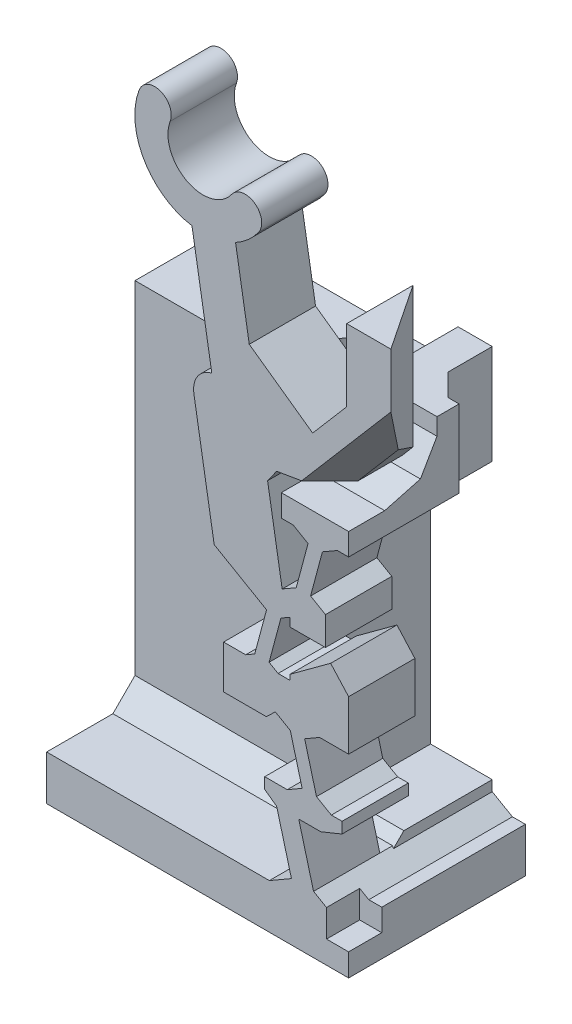
SolidWorks part; units mm, degrees
material "Nylon 6/12"
ref_plane "Front Plane" through (0, 0, 0) normal (0, 0, 1) x (1, 0, 0)
ref_plane "Top Plane" through (0, 0, 0) normal (0, 1, 0) x (1, 0, 0)
ref_plane "Right Plane" through (0, 0, 0) normal (1, 0, 0) x (0, 0, -1)
sketch "Sketch-SkeletonConfigUp" plane through (0, 0, 0) normal (0, 0, 1) x (1, 0, 0)
  line L0 (0, 0) -> (0, -50000) construction
  line L1 (0, 0) -> (4.5811, 6.2164) construction
  line L2 (9.8143, 13.3177) -> (4.5811, 13.945) construction
  line L3 (4.5811, 13.945) -> (2.9713, 10.4094) construction
  line L4 (2.9713, 10.4094) -> (4.5811, 6.2164) construction
  line L5 (4.5811, 13.945) -> (6.2429, 19.1409) construction
  line L6 (2.9713, 10.4094) -> (0.0405, 27.8193) construction
  line L7 (4.5811, 6.2164) -> (9.8143, 13.3177) construction
  line L8 (-587.3593, -797.0242) -> (9.8143, 13.3177) construction
  dimension "D2" = 7.7221
  dimension "D3" = 8.8212
  dimension "D4" = 5.2707
  dimension "D5" = 119.553
  dimension "D6" = 3.8848
  dimension "D7" = 5.4552
  dimension "D8" = 17.6549
  dimension "D9" = 4.4914
  dimension "D10" = 6.745
  dimension "D11" = 145.964
  dimension "D12" = 143.612
sketch "Sketch-SkeletonConfigDown" plane through (0, 0, 0) normal (0, 0, 1) x (1, 0, 0)
  line L0 (0, 0) -> (0, -50000) construction
  line L1 (0, 0) -> (4.5811, 6.2164) construction
  line L2 (9.8143, 13.3177) -> (4.5811, 13.945) construction
  line L3 (4.5811, 13.945) -> (6.1909, 10.4094) construction
  line L4 (6.1909, 10.4094) -> (4.5811, 6.2164) construction
  line L5 (4.5811, 13.945) -> (1.753, 18.6098) construction
  line L6 (6.1909, 10.4094) -> (-8.8652, 19.6294) construction
  line L7 (4.5811, 6.2164) -> (9.8143, 13.3177) construction
  line L8 (-589.9357, -800.5203) -> (9.8143, 13.3177) construction
  dimension "D2" = 7.7221
  dimension "D3" = 8.8212
  dimension "D4" = 5.2707
  dimension "D5" = 119.553
  dimension "D6" = 3.8848
  dimension "D7" = 5.4552
  dimension "D8" = 17.6549
  dimension "D9" = 4.4914
  dimension "D10" = 6.745
  dimension "D11" = 145.964
  dimension "D1" = 143.612
ref_plane "Plane-Cam Base" through (9.128, 0, 0) normal (1, 0, 0) x (0, 0, -1)
ref_plane "Plane-Down-to-Up Derailleur Clearance" through (6.628, 0, 0) normal (1, 0, 0) x (0, 0, -1)
ref_plane "Plane-Cam Cavity Roof" through (5.128, 0, 0) normal (1, 0, 0) x (0, 0, -1)
sketch "Sketch-SwitchBossUp" plane through (0, 0, 0) normal (0, 0, 1) x (1, 0, 0)
  line L0 (3.5811, 11.4759) -> (3.5811, 12.945) construction
  line L2 (6.5405, 21.1774) -> (6.5405, 24.4384)
  line L3 (6.5405, 24.4384) -> (8.5405, 24.4384)
  line L4 (8.5405, 24.4384) -> (8.5405, 20.4384)
  line L5 (5.5811, 12.5552) -> (5.5811, 11.263)
  line L7 (1.5115, 25.1048) -> (2.5464, 18.9575)
  line L8 (-0.4607, 24.7728) -> (0.4359, 19.4465)
  line L9 (2.9713, 10.4094) -> (0.0405, 27.8193) construction
  line L11 (-0.0396, 22.2712) -> (1.9326, 22.6032) construction
  line L15 (6.628, -55) -> (6.628, 55) construction
  line L16 (2.9713, 10.4094) -> (4.5811, 6.2164) construction
  line L17 (3.5811, 12.945) -> (3.5811, 14.945) construction
  line L18 (5.5811, 12.945) -> (5.5811, 14.945) construction
  line L19 (4.2561, 13.945) -> (4.9061, 13.945) construction
  line L20 (3.5811, 14.945) -> (5.5811, 14.945) construction
  line L21 (3.5811, 12.945) -> (5.5811, 12.945) construction
  line L22 (4.5811, 12.945) -> (4.5811, 14.945) construction
  line L23 (4.5811, 6.2164) -> (8.5405, 7.1023) construction
  line L24 (1.9713, 9.4094) -> (1.9713, 11.4094) construction
  line L25 (3.9713, 9.4094) -> (3.9713, 11.4094) construction
  line L26 (3.9713, 9.4094) -> (1.9713, 9.4094) construction
  line L27 (1.9713, 11.4094) -> (3.9713, 11.4094) construction
  line L28 (3.5811, 7.2164) -> (5.5811, 7.2164) construction
  line L29 (3.5811, 7.2164) -> (3.5811, 5.2164) construction
  line L30 (5.5811, 7.2164) -> (5.5811, 5.2164) construction
  line L31 (3.5811, 5.2164) -> (5.5811, 5.2164) construction
  line L32 (4.9061, 6.2164) -> (4.2561, 6.2164) construction
  line L40 (3.2963, 10.4094) -> (2.6463, 10.4094) construction
  line L43 (2.874, 4.5093) -> (0.7934, 4.5093) construction
  line L51 (4.9929, 19.3693) -> (2.5464, 18.9575)
  line L66 (0.0405, 27.8193) -> (0.0405, 50027.8193) construction
  line L74 (0.5445, 12.7775) -> (-0.3728, 18.2264)
  line L75 (0.3841, 13.7302) -> (2.3564, 14.0622) construction
  line L76 (5.5811, 11.263) -> (5.5811, 12.5552) construction
  line L80 (5.8152, 10.763) -> (6.628, 9.8603)
  line L81 (8.5405, 1033.6218) -> (8.5405, 20.4384) construction
  line L82 (2.5464, 18.9575) -> (3.5585, 12.945) construction
  line L83 (3.6203, 12.5779) -> (2.8784, 16.9852)
  line L84 (2.8784, 16.9852) -> (6.0405, 17.5175)
  line L85 (6.9307, 9.5241) -> (8.5405, 7.7363) construction
  line L88 (3.5811, 16.3347) -> (6.8573, 16.3347)
  line L92 (3.7762, 8.3129) -> (6.9307, 9.5241) construction
  line L93 (6.3311, 4.3289) -> (5.3706, 3.937)
  line L95 (2.5464, 18.9575) -> (2.8784, 16.9852) construction
  line L96 (2.7124, 17.9713) -> (8.5405, 18.9524) construction
  line L97 (2.7124, 17.9713) -> (1.7262, 17.8053) construction
  line L98 (1.9713, 9.1744) -> (0.9713, 9.1744)
  line L99 (0.9713, 9.1744) -> (0.9713, 7.2164)
  line L100 (0.9713, 7.2164) -> (2.9061, 7.2164)
  line L101 (4.5811, 6.2164) -> (6.9307, 9.5241) construction
  line L103 (0.0405, 27.8193) -> (1.9448, 26.4638) construction
  line L104 (6.9307, 9.5241) -> (8.5405, 7.7363) construction
  line L106 (13.4416, 14.945) -> (5.5811, 14.945) construction
  line L107 (1.9713, 9.4094) -> (1.9713, 9.1744) construction
  line L109 (0.0405, 27.8193) -> (-2.1498, 28.6358) construction
  line L110 (8.5405, 20.4384) -> (6.0405, 17.5175)
  line L111 (6.628, 9.8603) -> (6.628, 8.3653)
  line L112 (6.628, 9.8603) -> (6.9307, 9.5241) construction
  line L113 (2.8311, 4.8267) -> (2.8311, 4.3267)
  line L114 (7.3693, 7.7363) -> (7.3563, 7.7363) construction
  line L115 (6.8573, 16.3347) -> (13.4416, 16.3347)
  line L116 (13.4416, 16.3347) -> (13.4416, -1.1653)
  line L117 (13.4416, -1.1653) -> (5.0405, -1.1653)
  line L119 (10.4375, 14.0252) -> (10.4375, 2.1692)
  line L121 (5.0405, -1.1653) -> (5.0405, 1.437) construction
  line L122 (8.237, 12.8031) -> (10.8393, 12.8031) construction
  line L123 (10.8393, 12.8031) -> (13.4416, 12.8031) construction
  line L124 (10.4375, 2.1692) -> (9.128, 0.8597)
  line L125 (8.5405, 7.5847) -> (13.4416, 7.5847) construction
  line L127 (5.5811, 15.3347) -> (5.5811, 14.945) construction
  line L130 (6.0405, 0.8597) -> (9.128, 0.8597)
  line L132 (2.8311, 4.3267) -> (3.3706, 3.937)
  line L133 (2.9713, 10.4094) -> (6.1909, 10.4094) construction
  line L134 (4.5811, 10.4094) -> (4.5811, 13.945) construction
  line L135 (4.5811, 10.4094) -> (4.5811, 6.2164) construction
  line L137 (3.9713, 9.4094) -> (5.5811, 7.2164) construction
  line L139 (5.8152, 10.763) -> (3.9713, 9.4094)
  line L141 (4.0405, 1.437) -> (3.0405, 0.8597)
  line L142 (3.0405, 0.8597) -> (3.0405, -1.1653)
  line L143 (8.5405, 20.4384) -> (8.5405, 18.9524) construction
  line L145 (8.5405, 17.9384) -> (8.5405, -49992.0368) construction
  line L147 (5.5811, 11.263) -> (5.5811, 12.5552) construction
  line L149 (6.3311, 4.8289) -> (6.3311, 4.3289)
  line L150 (3.0405, -1.1653) -> (5.0405, -1.1653)
  line L151 (3.3706, 3.937) -> (5.3706, 3.937) construction
  line L152 (4.792, 14.945) -> (4.2561, 12.945)
  line L153 (5.442, 14.945) -> (4.9061, 12.945)
  line L157 (3.5811, 16.3347) -> (3.5811, 15.3347)
  line L158 (6.117, 15.3347) -> (9.128, 15.3347)
  line L162 (3.5642, 11.4094) -> (3.0283, 9.4094)
  line L164 (2.9142, 11.4094) -> (2.3783, 9.4094)
  line L169 (3.9882, 7.2164) -> (4.5241, 5.2164)
  line L170 (5.1741, 5.2164) -> (4.6382, 7.2164)
  line L176 (4.6382, 7.2164) -> (5.315, 7.6072)
  line L177 (5.5811, 7.2164) -> (5.5811, 7.6072) construction
  line L180 (3.5811, 5.2164) -> (3.5811, 4.8267) construction
  line L181 (3.5811, 4.8267) -> (2.8311, 4.8267)
  line L184 (5.5811, 5.2164) -> (5.5811, 4.8267) construction
  line L186 (9.128, -55) -> (9.128, 55) construction
  line L187 (2.3783, 9.4094) -> (1.9713, 9.1744)
  line L188 (3.0283, 9.4094) -> (3.4354, 9.1744)
  line L189 (3.5642, 11.4094) -> (3.9713, 11.6444)
  line L190 (2.9142, 11.4094) -> (0.5445, 12.7775)
  line L191 (3.9713, 11.4094) -> (3.9713, 11.6444) construction
  line L192 (3.9713, 11.6444) -> (3.9713, 11.263)
  line L193 (4.9061, 12.945) -> (5.5811, 12.5552)
  line L194 (4.2561, 12.945) -> (3.6203, 12.5779)
  line L195 (3.9713, 11.263) -> (5.5811, 11.263)
  line L196 (3.9713, 9.4094) -> (3.9713, 9.1744)
  line L197 (3.5811, 7.2164) -> (3.5811, 7.6072) construction
  line L200 (5.8453, 4.8289) -> (6.3311, 4.8289)
  line L201 (2.8311, 4.3267) -> (2.8311, 3.937) construction
  line L202 (2.8311, 3.937) -> (3.3706, 3.937) construction
  line L203 (10.4375, 14.0252) -> (9.128, 15.3347)
  line L204 (5.0405, 1.437) -> (3.0405, 1.437) construction
  line L205 (3.0405, 1.437) -> (3.0405, 0.8597) construction
  line L206 (5.0405, 1.437) -> (6.0405, 0.8597)
  line L207 (8.5405, 18.9524) -> (8.5405, 17.9384) construction
  line L208 (6.0405, 17.5175) -> (8.5405, 17.9384) construction
  line L209 (8.5405, 20.4384) -> (8.5405, 17.9384) construction
  line L210 (6.5405, 21.1774) -> (4.9929, 19.3693)
  line L211 (5.0405, 1.437) -> (4.3706, 3.937)
  line L212 (4.0405, 1.437) -> (3.3706, 3.937)
  line L213 (5.3706, 3.937) -> (4.3706, 3.937)
  line L214 (4.792, 14.945) -> (4.1169, 15.3347)
  line L215 (4.1169, 15.3347) -> (3.5811, 15.3347)
  line L216 (5.442, 14.945) -> (6.117, 15.3347)
  line L217 (5.5811, 12.945) -> (5.5811, 12.5552) construction
  line L218 (5.442, 14.945) -> (5.442, 15.3347) construction
  line L219 (6.117, 15.3347) -> (4.1169, 15.3347) construction
  line L220 (3.5811, 4.8267) -> (5.5811, 4.8267) construction
  line L221 (4.5241, 5.2164) -> (3.8491, 4.8267)
  line L222 (3.8491, 4.8267) -> (3.5811, 4.8267)
  line L223 (5.1741, 5.2164) -> (5.8453, 4.8289)
  line L224 (3.5811, 7.6072) -> (5.5811, 7.6072) construction
  line L225 (3.9882, 7.2164) -> (3.3114, 7.6072)
  line L226 (5.315, 7.6072) -> (6.628, 7.6072)
  line L227 (6.628, 7.6072) -> (6.628, 8.3653)
  line L228 (3.5811, 7.6072) -> (0.9713, 7.6072) construction
  line L229 (3.3114, 7.6072) -> (2.9061, 7.2164)
  line L230 (1.9713, 9.1744) -> (3.4354, 9.1744) construction
  line L231 (3.4354, 9.1744) -> (3.9713, 9.1744)
  arc A0 (1.5115, 25.1048) -> (2.5558, 26.0289) centre (0.0405, 27.8193) ccw
  arc A1 (-0.4607, 24.7728) -> (-2.8525, 28.8978) centre (0.0405, 27.8193) cw
  arc A2 (-2.8525, 28.8978) -> (-1.447, 28.3738) centre (-2.1498, 28.6358) cw
  arc A3 (2.5558, 26.0289) -> (1.3338, 26.8987) centre (1.9448, 26.4638) ccw
  arc A4 (-1.447, 28.3738) -> (1.3338, 26.8987) centre (0.0405, 27.8193) ccw
  arc A5 (3.5811, 12.945) -> (3.5811, 14.945) centre (3.1778, 13.945) ccw construction
  arc A6 (5.5811, 12.945) -> (5.5811, 14.945) centre (5.9843, 13.945) cw construction
  arc A7 (2.5293, 9.921) -> (1.9713, 11.4094) centre (1.568, 10.4094) ccw construction
  arc A8 (3.9713, 11.4094) -> (3.9713, 9.4094) centre (4.3745, 10.4094) ccw construction
  arc A9 (3.5811, 7.2164) -> (3.5811, 5.2164) centre (3.1779, 6.2164) cw construction
  arc A10 (5.5811, 7.2164) -> (5.5811, 5.2164) centre (5.9844, 6.2164) ccw construction
  arc A19 (-0.3728, 18.2264) -> (0.4359, 19.4465) centre (0.6836, 18.4042) cw
  circle A28 centre (0.0405, 27.8193) radius 2.3375 construction
  arc A29 (1.9713, 9.4094) -> (2.5293, 9.921) centre (1.568, 10.4094) ccw construction
  point P53 (4.5811, 13.945)
  point P63 (2.9713, 10.4094)
  point P93 (0.9465, 22.4372)
  point P159 (3.9713, 11.6444)
  point P164 (0.5179, 12.9353)
  dimension "D23" = 1.5875
  dimension "D24" = 0.75
  dimension "D2" = 2
  dimension "D5" = 2
  dimension "D6" = 0.65
  dimension "D8" = 42
  dimension "D7" = 2
  dimension "D11" = 8.5
  dimension "D14" = 7.5
  dimension "D4" = 3
  dimension "D16" = 42
  dimension "D17" = 0.5
  dimension "D20" = 3.5
  dimension "D21" = 1
  dimension "D18" = 45
  dimension "D9" = 17.5
  dimension "D22" = 1
  dimension "D15" = 45
  dimension "D38" = 2
  dimension "D39" = 0.5
  dimension "D41" = 1
  dimension "D42" = 45
  dimension "D43" = 120
  dimension "D44" = 2
  dimension "D45" = 2.5
  dimension "D46" = 2.5
  dimension "D47" = 4
  dimension "D48" = 2
  dimension "D10" = 15
  dimension "D12" = 2.5
  dimension "D13" = 1
  dimension "D19" = 1
  dimension "D25" = 15
  dimension "D26" = 120
  dimension "D35" = 120
  dimension "D27" = 15
  dimension "D28" = 30
  dimension "D29" = 30
  dimension "D30" = 30
  dimension "D36" = 30
  dimension "D31" = 30
  dimension "D32" = 30
  dimension "D33" = 30
  dimension "D34" = 30
  dimension "D37" = 15
extrude "Boss-Switch Body" add sketch "Sketch-SwitchBossUp" along normal blind 3
sketch "Sketch1" plane through (0, 0, 0) normal (0, 0, -1) x (-1, 0, 0)
  line L1 (-7.5811, -1.1653) -> (0.4122, -1.1653)
  line L2 (-7.5811, -1.1653) -> (-7.5811, 0.8597)
  line L4 (0.4122, -1.1653) -> (0.4122, 0.8597)
  line L5 (-3.5811, 18.8347) -> (-7.5811, 18.8347)
  line L10 (-7.5811, 18.8347) -> (-7.5811, 15.3347)
  line L11 (-4.0405, 1.437) -> (-5.0405, 1.437)
  line L12 (-7.5811, 15.3347) -> (-3.5811, 15.3347)
  line L13 (-4.0405, 1.437) -> (-3.0405, 0.8597)
  line L14 (-3.5811, 15.3347) -> (-3.5811, 18.8347)
  line L20 (-4.3706, 3.937) -> (-5.0405, 1.437) construction
  line L22 (-3.0405, -1.1653) -> (-13.4416, -1.1653) construction
  line L23 (-3.0405, 0.8597) -> (0.4122, 0.8597)
  line L24 (-5.0405, 1.437) -> (-6.0405, 0.8597)
  line L25 (-6.0405, 0.8597) -> (-7.5811, 0.8597)
  line L27 (-3.5811, 16.3347) -> (-3.5811, 15.3347) construction
  point P5 (-3.5811, 15.3347)
  dimension "D1" = 3.5
  dimension "D4" = 4
extrude "Boss-Flange Width" add sketch "Sketch1" along normal blind 5
ref_plane "Plane-Sta2Sit Groove" through (0.0405, 0, 0) normal (1, 0, 0) x (0, 0, -1)
ref_plane "Plane-Cam Outer Surface" through (-12.0395, 0, 0) normal (1, 0, 0) x (0, 0, -1)
ref_plane "Plane-FlangeTop" through (-7.0395, 0, 0) normal (1, 0, 0) x (0, 0, -1)
sketch "Sketch2" plane through (-7.0395, 0, 0) normal (1, 0, 0) x (0, 0, -1)
  line L0 (5, 15.3347) -> (-3, 15.3347) construction
  line L1 (5, 17.3347) -> (1, 17.3347)
  line L2 (5, 17.3347) -> (5, 15.3347)
  line L3 (5, 15.3347) -> (1, 15.3347)
  line L4 (1, 17.3347) -> (1, 15.3347)
  line L10 (-3, -1.1653) -> (-3, 16.3347) construction
  line L11 (5, 0.8597) -> (-3, 0.8597)
  line L12 (5, 0.8597) -> (5, -1.1653)
  line L13 (5, -1.1653) -> (-3, -1.1653)
  line L14 (-3, 0.8597) -> (-3, -1.1653)
  line L15 (0, 10.4094) -> (0, 27.8193) construction
  line L17 (5, 0.8597) -> (5, -1.1653) construction
  line L18 (-3, 0.8597) -> (0, 0.8597) construction
  dimension "D1" = 1
  dimension "D2" = 2
extrude "Boss-Flange Height" add sketch "Sketch2" along normal up to surface (11.6675 mm away)
sketch "Sketch10" plane through (0, 15.3347, 0) normal (0, 1, 0) x (1, 0, 0)
  line L0 (9.128, -55) -> (9.128, 55) construction
  line L1 (7.5811, 5) -> (5.128, 5)
  line L2 (7.5811, 5) -> (7.5811, 2)
  line L3 (7.5811, 2) -> (5.128, 2)
  line L5 (4.628, 7) -> (4.628, 1) construction
  line L6 (3.5811, 1) -> (-7.0395, 1) construction
  line L8 (5.128, 5) -> (5.128, 2)
  dimension "D1" = 1
  dimension "D2" = 0.5
  dimension "D3" = 4.5
extrude "Cut-Up-To-Down Derailleur Clearance" cut sketch "Sketch10" along normal up to next
sketch "Sketch17" plane through (0, 15.3347, 0) normal (0, -1, 0) x (1, 0, 0)
  line L0 (5.128, -5) -> (-7.0395, -5)
  line L1 (5.128, -5) -> (-7.0395, -5) construction
  line L2 (-7.0395, -5) -> (-7.0395, -1)
  line L3 (-7.0395, -1) -> (5.128, -1)
  line L4 (5.128, -1) -> (5.128, -5)
  line L5 (-7.0395, -1) -> (-7.0395, -5) construction
extrude "Boss-Flange Support" add sketch "Sketch17" along normal up to surface (14.475 mm away) up to face at (-1.9995, 0.8597, -1)
sketch "Sketch-HolePositions" plane through (0, -1.1653, 0) normal (0, -1, 0) x (1, 0, 0)
  line L0 (-7.0395, -3) -> (7.5811, -3) construction
  line L1 (7.5811, -5) -> (-7.0395, -5) construction
  line L2 (7.5811, -5) -> (7.5811, 0) construction
  line L4 (-7.0395, -22.2167) -> (-7.0395, 22.2167) construction
  line L5 (3.5811, -1) -> (3.5811, -5) construction
  point P6 (-4.0395, -3)
  point P7 (0.5811, -3)
  dimension "D1" = 3
  dimension "D2" = 3
  dimension "D3" = 2
sketch "Sketch6" plane through (0, -1.1653, 0) normal (0, -1, 0) x (-1, 0, 0)
  point P0 (4.0395, 3)
  point P3 (-0.5811, 3)
hole_wizard "Tap Drill for M2x0.4 Tap1" positions "Sketch6" profile "Sketch5" hole size "M2x0.4" standard "ANSI Metric" end condition through all
sketch "Sketch5" plane through (-4.0395, -1.1653, -3) normal (1, 0, 0) x (0, 0, -1)
  line L0 (0, 0) -> (0, 30.5511)
  line L1 (0, 30.5511) -> (0.8, 30.5511)
  line L2 (0.8, 30.5511) -> (0.8, 0)
  line L5 (0.8, 0) -> (0, 0)
  line L11 (0, -6.35) -> (0, 107.95) construction
  dimension "Thru Hole Dia." = 1.6
  dimension "Thru Hole Depth" = 30.5511
sketch "Sketch9" plane through (0, -1.1653, 0) normal (0, -1, 0) x (1, 0, 0)
  point P0 (-4.0395, -3)
  point P3 (0.5811, -3)
hole_wizard "M2 Clearance Hole2" positions "Sketch9" profile "Sketch8" hole size "M2" standard "ANSI Metric"
sketch "Sketch8" plane through (-4.0395, -1.1653, -3) normal (1, 0, 0) x (0, 0, -1)
  line L0 (0, 0) -> (0, 15.721)
  line L1 (0, 15.721) -> (1.2, 15)
  line L2 (1.2, 15) -> (1.2, 0)
  line L5 (1.2, 0) -> (0, 0)
  line L10 (0, 15.721) -> (-1.2, 15) construction
  line L11 (0, -6.35) -> (0, 107.95) construction
  dimension "Hole Dia." = 2.4
  dimension "Hole Depth" = 15
  dimension "Drill Angle" = 118
sketch "Sketch-Measurements for Derailleur Ramps" plane through (0, 0, 0) normal (0, 0, 1) x (1, 0, 0)
  line L0 (2.8784, 16.9852) -> (2.5464, 18.9575)
  line L1 (2.7124, 17.9713) -> (1.7262, 17.8053)
  line L2 (2.9713, 10.4094) -> (0.0405, 27.8193) construction
  line L3 (1.7262, 17.8053) -> (-1.8937, 15.3603)
  line L4 (6.1909, 10.4094) -> (-8.8652, 19.6294) construction
  line L5 (1.7262, 17.8053) -> (2.6012, 12.6077)
  line L6 (2.6012, 12.6077) -> (-1.8937, 15.3603)
  line L7 (-0.0837, 16.5828) -> (-0.0837, 17.8053)
  line L8 (-0.0837, 17.8053) -> (1.7262, 17.8053)
  line L9 (6.1909, 10.4094) -> (2.9713, 10.4094)
  line L10 (5.386, 8.3129) -> (3.7762, 8.3129)
  line L12 (6.1909, 10.4094) -> (4.5811, 6.2164) construction
  line L13 (4.5811, 8.3129) -> (4.5811, 8.7912)
  line L14 (4.5811, 6.2164) -> (5.386, 8.3129)
  line L15 (2.9713, 10.4094) -> (4.5811, 6.2164) construction
  line L16 (3.7762, 8.3129) -> (4.5811, 6.2164)
  line L17 (5.386, 8.3129) -> (5.386, 8.7912)
  dimension "D1" = 1.81
  dimension "D2" = 0.8049
sketch "Sketch12" plane through (0, 24.4384, 0) normal (0, 1, 0) x (1, 0, 0)
  line L0 (6.5405, 0) -> (8.5405, -3)
  line L1 (8.5405, -3) -> (8.5405, 0)
  line L2 (8.5405, 0) -> (6.5405, 0)
extrude "Cut-Up-to-Down Cantilever Slope" cut sketch "Sketch12" against normal up to next
ref_plane "Plane1" through (0, 7.1023, 0) normal (0, 1, 0) x (1, 0, 0)
sketch "Sketch-Derailleur Location" plane through (0, 7.1023, 0) normal (0, 1, 0) x (1, 0, 0)
  line L0 (8.5405, 0) -> (8.5405, -3)
  line L1 (4.0405, -3) -> (3.0405, -3) construction
  line L2 (-119237.4187, 0) -> (9.8143, 0) construction
  point P0 (8.5405, 0)
  point P8 (8.5405, -1.5)
ref_plane "Plane-Cantilever Cut" [suppressed] through (7.0848, 8.5204, -1.9058) normal (-0.6301, -0.7578, 0.1695) x (-0.7765, 0.6151, -0.1368)
sketch "Sketch14" [suppressed] plane through (7.0848, 8.5204, -1.9058) normal (-0.6301, -0.7578, 0.1695) x (-0.7765, 0.6151, -0.1368)
  line L0 (2.3023, -1.6911) -> (-0.3551, -1.6911)
  line L2 (2.3023, -4.3362) -> (2.3023, -1.6911)
  line L3 (-0.3551, -1.6911) -> (-0.3551, -4.4608)
  line L5 (-0.3551, -4.4608) -> (1.0087, -5.0843)
  line L6 (1.0087, -5.0843) -> (2.3023, -4.3362)
extrude "Cut-Down-to-Up Cantilever Slope" [suppressed] cut sketch "Sketch14" against normal up to next
sketch "Sketch16" plane through (0, 0, 0) normal (0, 0, -1) x (-1, 0, 0)
  line L0 (-7.5811, 18.8347) -> (-13.4416, 18.8347)
  line L1 (-13.4416, 18.8347) -> (-13.4416, -1.1653)
  line L2 (-13.4416, -1.1653) -> (-6.628, -1.1653)
  line L3 (-13.4416, -1.1653) -> (-5.0405, -1.1653) construction
  line L4 (-6.628, -1.1653) -> (-6.628, 5.2038)
  line L5 (-6.628, 5.2038) -> (-8.0037, 5.2038)
  line L6 (-8.0037, 5.2038) -> (-8.0037, 12.0484)
  line L7 (-8.0037, 12.0484) -> (-6.628, 12.0484)
  line L8 (-6.628, 12.0484) -> (-6.628, 17.9477)
  line L9 (-6.628, 55) -> (-6.628, -55) construction
  line L10 (-3.5811, 18.8347) -> (-6.5405, 18.8347) construction
  line L11 (-7.5811, 18.8347) -> (-6.628, 17.9477)
extrude "Cut-Down-to-Up Derailleur Clearance" cut sketch "Sketch16" against normal through all and the other way through all
ref_plane "Plane-Symmetry Plane" through (0, 0, 1.5) normal (0, 0, 1) x (1, 0, 0)
sketch "Sketch-Cable Center Point" plane through (0, 0, 1.5) normal (0, 0, 1) x (1, 0, 0)
  line L0 (0.0405, 27.8193) -> (0.1722, 27.0366)
  line L1 (2.9713, 10.4094) -> (0.0405, 27.8193) construction
  point P0 (0.0405, 27.8193)
  dimension "D1" = 0.7937
chamfer "Chamfer-Flange Support" distance 1.5 angle 45 1 edges at (3.5811, 17.3347, -3)
chamfer "Chamfer-Flange Support 2" distance 1 angle 45 2 edges at (5.128, 17.0847, -2) (5.128, 15.3347, -1.5)
chamfer "Chamfer-Flange Support 3" distance 1 angle 45 1 edges at (-1.9995, 0.8597, -1)
sketch "Sketch18" plane through (6.628, 0, 0) normal (1, 0, 0) x (0, 0, -1)
  line L1 (-3, -0.1403) -> (-1.5, -0.1403)
  line L2 (-3, -0.1403) -> (-3, 1.437)
  line L3 (-3, 1.437) -> (-1.5, 1.437)
  line L4 (-1.5, -0.1403) -> (-1.5, 1.437)
  line L5 (0.5774, 1.437) -> (0, 1.437) construction
  line L6 (-3, -1.1653) -> (-3, 0.8597) construction
  line L7 (-3, 0.8597) -> (5, 0.8597) construction
  dimension "D1" = 1.5
  dimension "D2" = 1
extrude "Cut-Down-to-Up Derailleur Clearance 2" cut sketch "Sketch18" against normal blind 1
sketch "Sketch19" plane through (0, 0, 0) normal (0, 0, 1) x (1, 0, 0)
  line L7 (3.5811, 18.8983) -> (6.628, 18.8983)
  line L8 (6.628, 18.8983) -> (6.628, 16.3347)
  line L9 (6.628, 16.3347) -> (3.5811, 16.3347)
  line L10 (3.5811, 16.3347) -> (3.5811, 18.8983)
  line L11 (6.628, 16.3347) -> (6.628, 17.9477) construction
  point P4 (6.628, 18.8983)
extrude "Cut-Up-to-Down Cantilever Clearance" cut sketch "Sketch19" against normal up to surface (1 mm away) up to face at (1.4435, 12.7784, -1)
chamfer "Chamfer1" distance 1 angle 60 1 edges at (5.1045, 16.3347, -1) first distance on face at (5.1045, 16.3347, 1)
chamfer "Chamfer3" distance 0.75 angle 60 1 edges at (3.5811, 16.7007, -1) first distance on face at (3.5811, 16.2811, 0.8)
chamfer "Chamfer4" distance 0.5 angle 60 1 edges at (4.205, 15.3347, -1) first distance on face at (5.0385, 15.3347, 0.5227)
chamfer "Chamfer5" distance 0.5 angle 45 1 edges at (2.8784, 16.9852, 1.5)
chamfer "Chamfer6" distance 2.5 angle 45 1 edges at (2.5464, 18.9575, 1.5)
chamfer "Chamfer7" distance 1 angle 45 1 edges at (7.2905, 18.978, 3)
sketch "Sketch22" plane through (0, 0, 0) normal (0, 0, 1) x (1, 0, 0)
  line L0 (6.628, 17.9477) -> (7.5811, 18.8347) construction
  line L1 (6.628, 18.8347) -> (7.5811, 18.8347) construction
  line L2 (6.628, 17.9477) -> (6.628, 18.8347) construction
  line L3 (6.628, 17.9477) -> (7.5811, 18.8347)
  line L4 (6.628, 18.8347) -> (7.5811, 18.8347)
  line L5 (6.628, 17.9477) -> (6.628, 18.8347)
extrude "Cut-Extrude3" cut sketch "Sketch22" against normal up to next
chamfer "Chamfer8" distance 0.5 angle 45 1 edges at (5.1045, 16.3347, 0) first distance on face at (4.2965, 17.2286, -0.5161)
sketch "Sketch23" plane through (0, 0, -1) normal (0, 0, 1) x (1, 0, 0)
  line L0 (5.128, 1.8597) -> (2.3369, 1.8597)
  line L1 (-7.0395, 1.8597) -> (5.128, 1.8597) construction
  line L2 (2.3369, 1.8597) -> (2.3369, 14.3347)
  line L3 (2.3369, 14.3347) -> (5.128, 14.3347)
  line L4 (5.128, 14.3347) -> (5.128, 1.8597)
extrude "Cut-Extrude4" cut sketch "Sketch23" against normal through all
equation "\"axle-diameter\"=2"
equation "\"switch-thickness\"=12"
equation "\"base-width\"=4.0"
equation "\"axle-bushing-radius\"=3"
equation "\"clearance\"= 0.25"
equation "\"arm-width\"=1.5"
equation "\"min-diameter\"=70"
equation "\"alpha\"=143.6120"
equation "\"gamma\"=119.5526"
equation "\"delta\"=145.9637"
equation "\"epsilon\"=6.7452"
equation "\"l_AB\"=8.8212"
equation "\"l_AC\"=4.4914"
equation "\"l_BD\"=5.2707"
equation "\"l_CD\"=3.8848"
equation "\"l_CE\"=17.6549"
equation "\"l_DF\"=5.4552"
equation "\"l_OA\"=7.7221"
equation "\"D2@Sketch-SkeletonConfigUp\" = \"l_OA\""
equation "\"D3@Sketch-SkeletonConfigUp\" = \"l_AB\""
equation "\"D4@Sketch-SkeletonConfigUp\" = \"l_BD\""
equation "\"D5@Sketch-SkeletonConfigUp\" = \"gamma\""
equation "\"D6@Sketch-SkeletonConfigUp\" = \"l_CD\""
equation "\"D7@Sketch-SkeletonConfigUp\" = \"l_DF\""
equation "\"D8@Sketch-SkeletonConfigUp\" = \"l_CE\""
equation "\"D9@Sketch-SkeletonConfigUp\" = \"l_AC\""
equation "\"D_groove\"=3.175"
equation "\"D7@Sketch-SkeletonConfigDown\" = \"l_DF\""
equation "\"D6@Sketch-SkeletonConfigDown\" = \"l_CD\""
equation "\"D2@Sketch-SkeletonConfigDown\" = \"l_OA\""
equation "\"D3@Sketch-SkeletonConfigDown\" = \"l_AB\""
equation "\"D9@Sketch-SkeletonConfigDown\" = \"l_AC\""
equation "\"D8@Sketch-SkeletonConfigDown\" = \"l_CE\""
equation "\"D5@Sketch-SkeletonConfigDown\" = \"gamma\""
equation "\"D4@Sketch-SkeletonConfigDown\" = \"l_BD\""
equation "\"D1@Sketch-SkeletonConfigDown\" = \"alpha\""
equation "\"hinge_length\"=1.5"
equation "\"hinge_depth\"=0.25"
equation "\"D10@Sketch-SkeletonConfigUp\"=\"epsilon\""
equation "\"D11@Sketch-SkeletonConfigUp\"=\"delta\""
equation "\"D12@Sketch-SkeletonConfigUp\"=\"alpha\""
equation "\"D11@Sketch-SkeletonConfigDown\"=\"delta\""
equation "\"D10@Sketch-SkeletonConfigDown\"=\"epsilon\""
equation "\"EE_dx\"=8.9056"
equation "\"EE_dy\"=8.1898"
equation "\"r_groove\"=\"D_groove\"/2"
equation "\"t_wall\"=25.4/16"
equation "\"width_lower\"=\"D_groove\"+\"t_wall\""
equation "\"cable_to_bottom\"=30.6257"
equation "\"switch_EE-up_base_dy\"=24"
equation "\"switch_EE-down_base_dy\"=16"
equation "\"D_axle\"=25.4/8"
equation "\"D_up_to_down\"=16"
equation "\"D_down_to_up\"=25"
equation "\"t_cam_base\"=7.5"
equation "\"D23@Sketch-SwitchBossUp\"=\"D_groove\"/2"
equation "\"D1@Sketch-Cable Center Point\"=\"D_groove\"/4"
